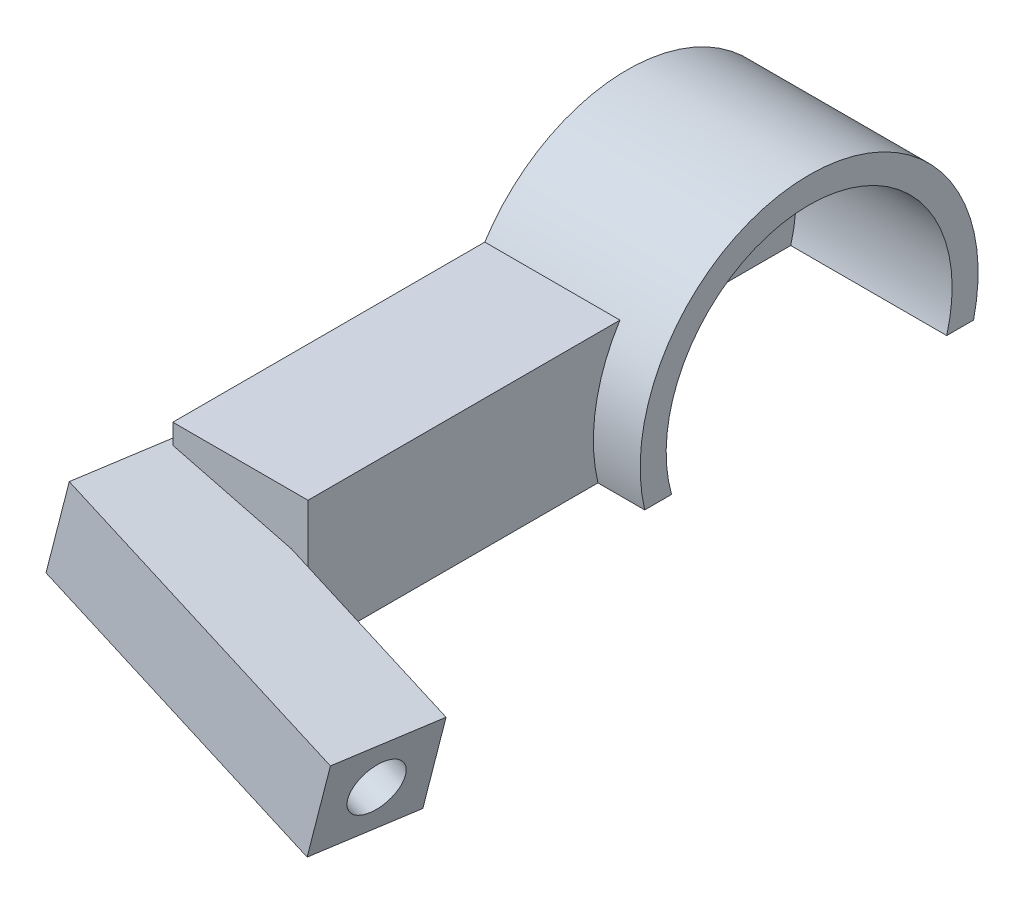
SolidWorks part; units mm, degrees
material "1060 合金"
ref_plane "前视基准面" through (0, 0, 0) normal (0, 0, 1) x (1, 0, 0)
ref_plane "上视基准面" through (0, 0, 0) normal (0, 1, 0) x (1, 0, 0)
ref_plane "右视基准面" through (0, 0, 0) normal (1, 0, 0) x (0, 0, -1)
sketch "草图2" plane through (0, 0, 0) normal (1, 0, 0) x (0, 0, -1)
  line L0 (-31.6228, -7.5) -> (31.6228, -7.5)
  line L1 (0, -7.5) -> (0, 41.6424) construction
  arc A0 (31.6228, -7.5) -> (-31.6228, -7.5) centre (0, 0) ccw
  point P6 (0, 32.5)
  dimension "D1" = 65
  dimension "D2" = 40
extrude "凸台-拉伸1" add sketch "草图2" along normal blind 35
sketch "草图6" plane through (0, 0, 0) normal (-1, 0, 0) x (0, 0, 1)
  line L0 (31.6228, -7.5) -> (-31.6228, -7.5) construction
  line L1 (27.3861, -7.5) -> (87.3861, -7.5)
  line L2 (27.3861, -7.5) -> (27.3861, 17.5)
  line L3 (27.3861, 17.5) -> (87.3861, 17.5)
  line L4 (87.3861, -7.5) -> (87.3861, 17.5)
  arc A0 (31.6228, -7.5) -> (-31.6228, -7.5) centre (0, 0) ccw construction
  dimension "D1" = 25
  dimension "D2" = 60
extrude "凸台-拉伸2" add sketch "草图6" against normal blind 26
sketch "草图4" plane through (35, 0, 0) normal (1, 0, 0) x (0, 0, -1)
  circle A0 centre (0, 0) radius 27.5
  dimension "D1" = 55
extrude "切除-拉伸1" cut sketch "草图4" against normal blind 30
sketch "草图9" plane through (0, 0, 0) normal (-1, 0, 0) x (0, 0, 1)
  line L0 (0, -7.5) -> (-31.9114, 6.1574)
  line L1 (87.3861, -7.5) -> (-31.6228, -7.5) construction
  line L5 (-31.6228, -7.5) -> (87.3861, -7.5)
  line L6 (87.3861, -7.5) -> (87.3861, 17.5)
  line L7 (87.3861, 17.5) -> (27.3861, 17.5)
  line L8 (-31.6228, -7.5) -> (0, -7.5)
  arc A0 (27.3861, 17.5) -> (-31.6228, -7.5) centre (0, 0) ccw construction
  arc A2 (27.3861, 17.5) -> (-31.6228, -7.5) centre (0, 0) ccw
  arc A3 (-31.9114, 6.1574) -> (-31.6228, -7.5) centre (0, 0) ccw
  dimension "D1" = 0
extrude "切除-拉伸4" [suppressed] cut sketch "草图9" against normal through all
sketch "草图7" [suppressed] plane through (0, 17.5, 0) normal (0, 1, 0) x (1, 0, 0)
  line L0 (13, -77.3861) -> (13, -57.3861) construction
  line L1 (9, -77.3861) -> (9, -57.3861)
  line L2 (17, -77.3861) -> (17, -57.3861)
  line L3 (26, -87.3861) -> (0, -87.3861) construction
  line L4 (26, -27.3861) -> (0, -27.3861) construction
  line L5 (13, -87.3861) -> (13, -12.9357) construction
  arc A0 (9, -77.3861) -> (17, -77.3861) centre (13, -77.3861) ccw
  arc A1 (17, -57.3861) -> (9, -57.3861) centre (13, -57.3861) ccw
  point P2 (13, -67.3861)
  dimension "D1" = 10
  dimension "D2" = 8
  dimension "D3" = 30
extrude "切除-拉伸2" [suppressed] cut sketch "草图7" against normal through all
sketch "草图8" [suppressed] plane through (0, 0, 0) normal (-1, 0, 0) x (0, 0, 1)
  line L0 (47.3861, 5.6103) -> (62.3861, 5.6103) construction
  line L1 (47.3861, 9.1713) -> (62.3861, 9.1713)
  line L2 (47.3861, 2.0494) -> (62.3861, 2.0494)
  line L3 (87.3861, -7.5) -> (87.3861, 17.5) construction
  arc A0 (47.3861, 9.1713) -> (47.3861, 2.0494) centre (47.3861, 5.6103) ccw
  arc A1 (62.3861, 2.0494) -> (62.3861, 9.1713) centre (62.3861, 5.6103) ccw
  point P2 (54.8861, 5.6103)
  dimension "D1" = 25
  dimension "D2" = 20
extrude "切除-拉伸3" [suppressed] cut sketch "草图8" against normal through all
sketch "草图11" [suppressed] plane through (0, 0, 87.3861) normal (0, 0, 1) x (1, 0, 0)
  line L0 (1.6724, 5.0579) -> (24.5339, 5.0579) construction
  line L1 (13.1031, 14.2856) -> (13.1031, -4.1697) construction
  circle A0 centre (13.1031, 5.0579) radius 8
  dimension "D1" = 16
sketch3d "3D草图3"
  line L0 (0, 0, 0) -> (17, 0, 0) construction
  line L1 (17, 0, 0) -> (17, 0, 97) construction
  line L3 (47.182, 0, 97) -> (47.182, 0, 100.8954) construction
  line L4 (17, 0, 97) -> (47.182, 0, 97) construction
  line L5 (47.182, 0, 100.8954) -> (47.182, -7.745, 100.8954) construction
  line L6 (47.182, -7.745, 100.8954) -> (-13.182, 7.745, 93.1046)
  dimension "D2" = 17
  dimension "D3" = 97
ref_axis "基准轴1" through (47.182, -7.745, 100.8954) along (-0.9611, 0.2466, -0.124)
ref_plane "基准面1" through (17, 0, 97) normal (-0.9611, 0.2466, -0.124) x (-0.1202, 0.0308, 0.9923)
sketch "草图12" plane through (17, 0, 97) normal (-0.9611, 0.2466, -0.124) x (-0.1202, 0.0308, 0.9923)
  line L1 (-10, -9) -> (10, -9)
  line L2 (-10, -9) -> (-10, 9)
  line L3 (-10, 9) -> (10, 9)
  line L4 (10, -9) -> (10, 9)
  line L5 (-10, -9) -> (10, 9) construction
  line L6 (-10, 9) -> (10, -9) construction
  circle A0 centre (0, 0) radius 5
  point P0 (0, 0)
  dimension "D1" = 10
  dimension "D2" = 18
  dimension "D3" = 20
extrude "凸台-拉伸3" add sketch "草图12" along normal blind 22 and the other way blind 38
ref_plane "基准面3" [suppressed] through (-1.1867, -4.6247, 0) normal (-0.2486, -0.9686, 0) x (-0.9686, 0.2486, 0)
other "使用曲面切除5" [suppressed]
move or copy body "实体-移动/复制1" [suppressed] bodies to move or copy 107
